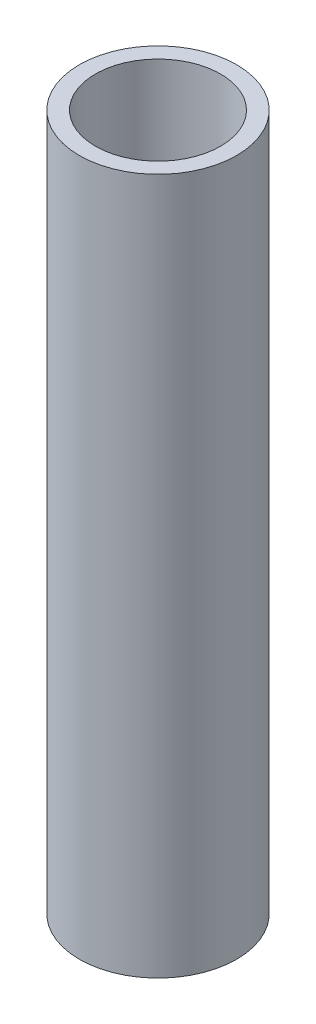
SolidWorks part; units mm, degrees
ref_plane "Front Plane" through (0, 0, 0) normal (0, 0, 1) x (1, 0, 0)
ref_plane "Top Plane" through (0, 0, 0) normal (0, 1, 0) x (1, 0, 0)
ref_plane "Right Plane" through (0, 0, 0) normal (1, 0, 0) x (0, 0, -1)
sketch "Sketch1" plane through (0, 0, 0) normal (0, 1, 0) x (1, 0, 0)
  circle A1 centre (0, 0) radius 11.811
  dimension "D1" = 23.622
extrude "Boss-Extrude1" add sketch "Sketch1" against normal blind 104.521
sketch "Sketch2" plane through (0, 0, 0) normal (0, 1, 0) x (1, 0, 0)
  circle A0 centre (0, 0) radius 9.398
  dimension "D1" = 18.796
extrude "Cut-Extrude1" cut sketch "Sketch2" against normal offset from surface (99.441 mm away) 5.08 up to face at (0, -104.521, 11.811)
sketch "Sketch3" plane through (0, 0, 0) normal (0, 1, 0) x (1, 0, 0)
  circle A0 centre (0, 0) radius 6.096
  dimension "D1" = 12.192
extrude "Cut-Extrude2" cut sketch "Sketch3" against normal through all
ref_axis "Axis1" through (0, 5.2261, 0) along (0, -1, 0)
